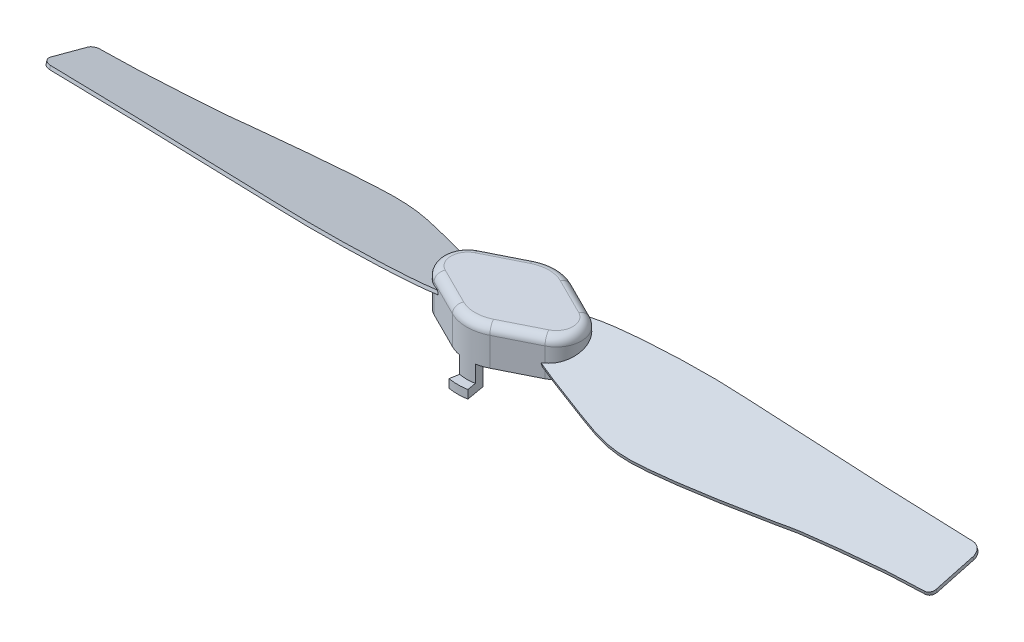
SolidWorks part; units mm, degrees
ref_plane "前视基准面" through (0, 0, 0) normal (0, 0, 1) x (1, 0, 0)
ref_plane "上视基准面" through (0, 0, 0) normal (0, 1, 0) x (1, 0, 0)
ref_plane "右视基准面" through (0, 0, 0) normal (1, 0, 0) x (0, 0, -1)
sketch "草图1" plane through (0, 0, 0) normal (0, 1, 0) x (1, 0, 0)
  line L0 (-6, 0) -> (6, 0) construction
  line L1 (0, 3) -> (0, -3) construction
  line L2 (0, 3) -> (-6, 0)
  line L3 (0, -3) -> (-6, 0)
  line L4 (0, -3) -> (6, 0)
  line L5 (6, 0) -> (0, 3)
  point P4 (0, 0)
  point P7 (0, 0)
  dimension "D1" = 12
  dimension "D2" = 6
extrude "凸台-拉伸1" add sketch "草图1" along normal blind 3.2 from offset 2
sketch "草图2" plane through (0, 2, 0) normal (0, -1, 0) x (1, 0, 0)
  line L0 (-5.2231, 0) -> (5.5973, 0)
ref_plane "基准面1" through (0, 1.866, 0.5) normal (0, -0.9659, -0.2588) x (1, 0, 0)
ref_plane "基准面10" through (0, 3.7979, 1.0176) normal (0, -0.9659, -0.2588) x (1, 0, 0)
sketch "草图9" plane through (0, 3.7979, 1.0176) normal (0, -0.9659, -0.2588) x (1, 0, 0)
  line L0 (-26.7041, 0.3228) -> (-26.7041, -1.9457)
  line L1 (0, -3.4154) -> (-6, -0.5176) construction
  line L2 (-5.2231, -0.5176) -> (5.5973, -0.5176) construction
  arc A0 (-26.7041, 0.3228) -> (-26.3393, 0.6876) centre (-26.3393, 0.3228) cw
  arc A1 (-26.7041, -1.9457) -> (-26.1115, -2.5991) centre (-26.0475, -1.9457) ccw
  spline S0 degree 3 poles (-1.4329, -0.5176) (-2.7254, 0.2749) (-2.9583, 0.3643) (-7.6949, 1.9383) (-9.1523, 2.4326) (-12.9904, 2.1706) (-15.9072, 1.7478) (-19.0984, 1.266) (-18.8037, 1.1973) (-24.7636, 0.7055) (-25.802, 0.7264) (-26.3393, 0.6876) knots 0 0 0 0 0.27319 0.324145 0.488947 0.531153 0.703993 0.748506 0.931769 0.959209 1 1 1 1
  spline S1 degree 3 poles (-26.1115, -2.5991) (-22.9105, -2.689) (-24.116, -2.6478) (-17.5523, -2.8675) (-13.3297, -3.0646) (-9.2951, -3.2316) (-3.3383, -3.0619) (-1.3944, -1.9668) (2.5094, 0.1061) (-1.4329, -0.5176) knots 0 0 0 0 0.213914 0.269576 0.524729 0.582278 0.787522 0.818456 1 1 1 1
extrude "凸台-拉伸3" add sketch "草图9" along normal mid plane 0.2
sketch "草图10" plane through (0, 0, 0) normal (1, 0, 0) x (0, 0, -1)
  line L0 (0, 4.3399) -> (0, -0.6481) construction
pattern_circular "阵列(圆周)1" count 2 over 360 about axis through (0, 4.3399, 0) along (0, -1, 0) of "凸台-拉伸3" reverse direction yes
scale "缩放比例1" bodies to scale 111 110 scale about origin uniform scaling yes scale factor 2
fillet "圆角4" radius 3 4 edges at (-12, 9.3741, 0) (12, 9.3741, 0) (-12, 5.967, 0) (12, 5.967, 0)
fillet "圆角5" radius 5 2 edges at (0, 7.2, 6) (0, 7.2, -6)
fillet "圆角6" radius 1 8 edges at (-8.2918, 10.4, 0) (-4.4348, 10.4, -3.7826) (0, 10.4, -5.4098) (4.4348, 10.4, -3.7826) (8.2918, 10.4, 0) (4.4348, 10.4, 3.7826) (0, 10.4, 5.4098) (-4.4348, 10.4, 3.7826)
sketch "草图15" plane through (0, 4, 0) normal (0, -1, 0) x (1, 0, 0)
  line L0 (-0.9382, -5.321) -> (0, 0)
  line L1 (-0.9382, 5.321) -> (0, 0)
  line L2 (0, 0) -> (0.9382, 5.321)
  line L3 (0, 0) -> (0.9382, -5.321)
  line L4 (6.6334, 2.6833) -> (2.2361, 4.882)
  line L5 (-2.2361, 4.882) -> (-6.6334, 2.6833)
  line L6 (-6.6334, -2.6833) -> (-2.2361, -4.882)
  line L7 (2.2361, -4.882) -> (6.6334, -2.6833)
  line L8 (6.6334, 2.6833) -> (2.2361, 4.882)
  line L9 (-2.2361, 4.882) -> (-6.6334, 2.6833)
  line L10 (-6.6334, -2.6833) -> (-2.2361, -4.882)
  line L11 (2.2361, -4.882) -> (6.6334, -2.6833)
  line L12 (0, -1.76) -> (0, 1.76) construction
  circle A0 centre (0, 0) radius 4.3
  arc A4 (2.2361, 4.882) -> (-2.2361, 4.882) centre (0, 0.4098) ccw
  arc A5 (-6.6334, 2.6833) -> (-6.6334, -2.6833) centre (-5.2918, 0) ccw
  arc A6 (-2.2361, -4.882) -> (2.2361, -4.882) centre (0, -0.4098) ccw
  arc A7 (6.6334, -2.6833) -> (6.6334, 2.6833) centre (5.2918, 0) ccw
  arc A8 (2.2361, 4.882) -> (-2.2361, 4.882) centre (0, 0.4098) ccw
  arc A9 (-6.6334, 2.6833) -> (-6.6334, -2.6833) centre (-5.2918, 0) ccw
  arc A10 (-2.2361, -4.882) -> (2.2361, -4.882) centre (0, -0.4098) ccw
  arc A11 (6.6334, -2.6833) -> (6.6334, 2.6833) centre (5.2918, 0) ccw
  line M10 (6.6334, 2.6833) -> (2.2361, 4.882)
  arc M11 (2.2361, 4.882) -> (-2.2361, 4.882) centre (0, 0.4098) ccw
  line M12 (-2.2361, 4.882) -> (-6.6334, 2.6833)
  arc M13 (-6.6334, 2.6833) -> (-6.6334, -2.6833) centre (-5.2918, 0) ccw
  line M14 (-6.6334, -2.6833) -> (-2.2361, -4.882)
  arc M15 (-2.2361, -4.882) -> (2.2361, -4.882) centre (0, -0.4098) ccw
  line M16 (2.2361, -4.882) -> (6.6334, -2.6833)
  arc M17 (6.6334, -2.6833) -> (6.6334, 2.6833) centre (5.2918, 0) ccw
  dimension "D2" = 8.6
  dimension "D3" = 10
  dimension "D4" = 10
  dimension "D5" = 10
  dimension "D6" = 10
  dimension "D1" = 0
extrude "切除-拉伸2" cut sketch "草图15" against normal blind 2 contours A0 L3 L2 M15 M16 M17 M10 M11 | L3 A0 L2 | L2 A0 L1 | L0 A0 L3 | L1 A0 L0 | A0 L1 L0 M11 M12 M13 M14 M15 region at (-4.9466, 4, 0) region at (-2.0219, 4, 0) region at (0, 4, -2.8521) region at (4.9466, 4, 0) region at (0, 4, 2.8521) region at (2.0219, 4, 0)
sketch "草图17" plane through (0, 4, 0) normal (0, -1, 0) x (1, 0, 0)
  line L0 (-1.1287, 6.4013) -> (1.1287, -6.4013)
  line L1 (1.1287, 6.4013) -> (-1.1287, -6.4013)
  line L2 (0, -1.76) -> (0, 1.76) construction
  circle A0 centre (0, 0) radius 6.5
  arc A1 (0.9382, 5.321) -> (-0.9382, 5.321) centre (0, 0.4098) ccw construction
  arc A2 (0.9382, 5.321) -> (-0.9382, 5.321) centre (0, 0.4098) ccw
  arc A3 (-0.9382, -5.321) -> (0.9382, -5.321) centre (0, -0.4098) ccw construction
  arc A4 (-0.9382, -5.321) -> (0.9382, -5.321) centre (0, -0.4098) ccw
  arc A5 (-0.7467, -4.2347) -> (0.7467, -4.2347) centre (0, 0) ccw construction
  arc A6 (-0.7467, -4.2347) -> (0.7467, -4.2347) centre (0, 0) ccw
  arc A7 (0.7467, 4.2347) -> (-0.7467, 4.2347) centre (0, 0) ccw construction
  arc A8 (0.7467, 4.2347) -> (-0.7467, 4.2347) centre (0, 0) ccw
  line M3 (0.7467, 4.2347) -> (0.9382, 5.321)
  arc M4 (0.9382, 5.321) -> (-0.9382, 5.321) centre (0, 0.4098) ccw
  line M5 (-0.9382, 5.321) -> (-0.7467, 4.2347)
  arc M6 (-0.7467, 4.2347) -> (0.7467, 4.2347) centre (0, 0) cw
  dimension "D1" = 13
  dimension "D2" = 10
  dimension "D3" = 10
extrude "凸台-拉伸4" add sketch "草图17" along normal blind 1 contours L1 A0 L0 M4 | M6 M3 M4 M5 | A4 L1 A0 L0 | A6 L1 A4 L0 region at (0, 4, 5.9402) region at (0, 4, 4.8502) region at (0, 4, -5.9402) region at (0, 4, -4.8502)
scale "缩放比例2" scale about centroid uniform scaling yes scale factor 1.2
sketch "草图11" [suppressed] plane through (0, 0, 0) normal (0, -1, 0) x (1, 0, 0)
  circle A0 centre (0, 0) radius 1
  dimension "D1" = 2
extrude "切除-拉伸1" cut sketch "草图11" against normal blind 10
ref_plane "基准面11" through (0, 0, 10) normal (0, 0, 1) x (1, 0, 0)
mirror "镜向1" about plane through (0, 0, 10) normal (0, 0, 1) of bodies 120
delete or keep bodies "实体-删除/保留 1" type delete bodies bodies 120
